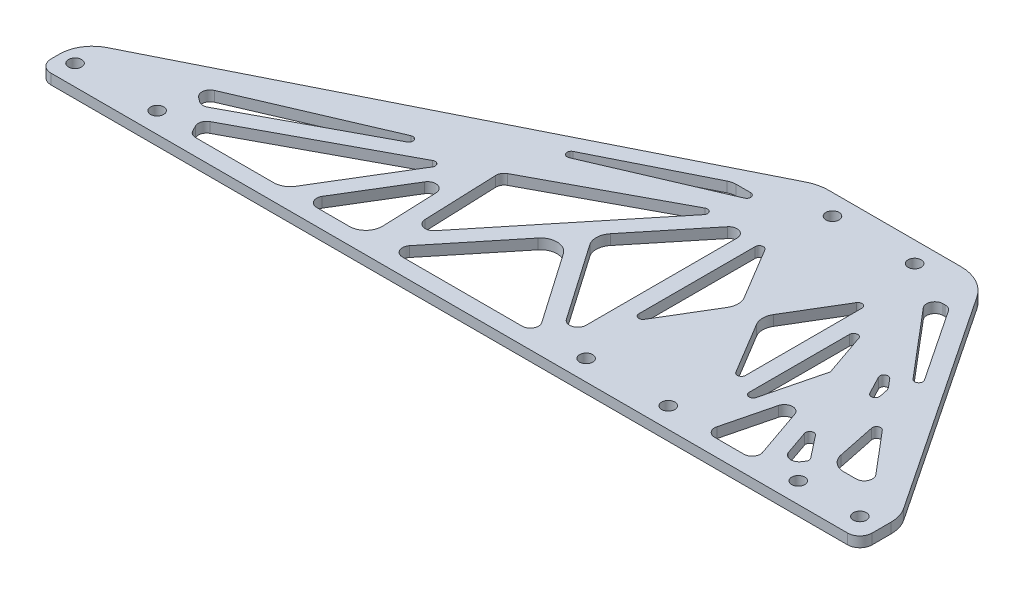
SolidWorks part; units mm, degrees
ref_plane "Front Plane" through (0, 0, 0) normal (0, 0, 1) x (1, 0, 0)
ref_plane "Top Plane" through (0, 0, 0) normal (0, 1, 0) x (1, 0, 0)
ref_plane "Right Plane" through (0, 0, 0) normal (1, 0, 0) x (0, 0, -1)
sketch "Sketch1" plane through (0, 0, 0) normal (0, 1, 0) x (1, 0, 0)
  line L0 (0, 0) -> (254, 0)
  line L2 (203.2, 88.9) -> (152.4, 88.9)
  line L4 (0, 0) -> (0, 12.7)
  line L5 (0, 12.7) -> (152.4, 88.9)
  line L6 (203.2, 88.9) -> (254, 12.7)
  line L7 (254, 12.7) -> (254, 0)
  line L8 (0, 6.35) -> (41.2306, 6.35) construction
  line L9 (254, 6.35) -> (220.1675, 6.35) construction
  line L10 (139.7, 82.55) -> (207.4333, 82.55) construction
  line L11 (156.6333, 76.2) -> (38.0113, 12.7) construction
  line L12 (38.0113, 12.7) -> (22.7185, 24.0592)
  line L13 (226.5259, 15.8112) -> (251.9259, 15.8112)
  line L20 (127, 76.2) -> (211.6667, 76.2)
  line L21 (226.5259, 15.8112) -> (215.9, 0)
  line L22 (38.0113, 12.7) -> (44.45, 0)
  line L23 (156.6333, 76.2) -> (27.2885, 20.6647) construction
  line L24 (156.6333, 76.2) -> (98.8302, 5.08) construction
  line L28 (194.7333, 76.2) -> (226.5259, 15.8112) construction
  line L31 (5.08, 9.5604) -> (153.5992, 83.82)
  line L32 (200.4813, 83.82) -> (153.5992, 83.82)
  line L33 (200.4813, 83.82) -> (248.92, 11.1619)
  line L34 (248.92, 11.1619) -> (248.92, 5.08)
  line L35 (5.08, 5.08) -> (248.92, 5.08)
  line L36 (5.08, 5.08) -> (5.08, 9.5604)
  line L37 (219.314, 5.08) -> (194.7333, 76.2) construction
  line L39 (194.7333, 76.2) -> (245.8205, 15.8112) construction
  line L40 (98.8302, 5.08) -> (97.3223, 44.45) construction
  line L41 (127.7318, 40.64) -> (152.3892, 5.08) construction
  line L42 (207.0237, 40.64) -> (198.1092, 5.08) construction
  line L83 (226.5259, 15.8112) -> (220.2769, 46.0056) construction
  line L84 (207.0237, 40.64) -> (226.5259, 15.8112) construction
  line L107 (97.3223, 44.45) -> (73.4302, 5.08) construction
  line L108 (156.6333, 76.2) -> (194.7333, 12.7) construction
  line L113 (194.7333, 76.2) -> (156.6333, 12.7) construction
  line L114 (155.6312, 78.534) -> (26.2864, 22.9986)
  line L115 (155.4346, 78.4393) -> (36.8125, 14.9393)
  line L116 (154.6622, 77.802) -> (101.1104, 11.9127)
  line L117 (156.6333, 12.7) -> (154.0933, 8.1397)
  line L118 (156.6333, 12.7) -> (194.7333, 12.7)
  line L119 (194.7333, 12.7) -> (200.3598, 0)
  line L120 (153.0965, 6.35) -> (197.5465, 6.35) construction
  line L123 (101.1104, 11.9127) -> (99.5369, 52.9951)
  line L124 (99.5369, 52.9951) -> (96.1931, 47.4852)
  line L125 (125.6445, 39.1927) -> (150.3019, 3.6327)
  line L126 (192.5553, 77.5068) -> (154.4553, 14.0068)
  line L127 (154.4553, 74.8932) -> (192.5553, 11.3932)
  line L128 (156.6333, 12.7) -> (156.6333, 76.2) construction
  line L129 (194.7333, 12.7) -> (194.7333, 76.2) construction
  line L130 (197.2733, 12.7) -> (197.2733, 76.2)
  line L131 (159.1733, 12.7) -> (159.1733, 76.2)
  line L132 (192.1933, 12.7) -> (192.1933, 76.2)
  line L133 (154.0933, 12.7) -> (154.0933, 76.2)
  line L134 (205.8201, 46.2844) -> (228.5234, 17.3801)
  line L137 (205.8201, 46.2844) -> (195.6454, 5.6976)
  line L138 (221.7147, 5.9097) -> (197.134, 77.0297)
  line L139 (192.4858, 75.0167) -> (224.2783, 14.6279)
  line L140 (229.0132, 16.3259) -> (222.7642, 46.5203)
  line L141 (157.6354, 73.866) -> (28.2906, 18.3307)
  line L142 (157.8321, 73.9607) -> (39.21, 10.4607)
  line L143 (158.6044, 74.598) -> (96.5501, -1.7527)
  line L144 (96.5501, -1.7527) -> (95.1077, 35.9049)
  line L145 (95.1077, 35.9049) -> (75.6017, 3.7622)
  line L146 (129.8191, 42.0873) -> (154.4765, 6.5273)
  line L147 (196.9114, 74.8932) -> (158.8114, 11.3932)
  line L148 (158.8114, 77.5068) -> (196.9114, 14.0068)
  line L149 (208.2273, 34.9956) -> (224.5284, 14.2422)
  line L150 (208.2273, 34.9956) -> (200.5729, 4.4624)
  line L151 (216.9134, 4.2503) -> (192.3327, 75.3703)
  line L152 (196.9809, 77.3833) -> (228.7734, 16.9944)
  line L153 (224.0386, 15.2964) -> (217.7896, 45.4908)
  line L154 (71.2588, 6.3978) -> (70.4591, 5.08)
  line L155 (36.8125, 14.9393) -> (35.7571, 14.3744)
  line L156 (39.21, 10.4607) -> (39.1601, 10.434)
  line L157 (154.0933, 12.7) -> (154.0933, 7.0799)
  line L158 (197.2733, 12.7) -> (197.2733, 6.9667)
  line L159 (224.5284, 14.2422) -> (225.0366, 13.5952)
  line L160 (229.0132, 16.3259) -> (229.1197, 15.8112)
  line L161 (192.7942, 74.5595) -> (243.8813, 14.1707)
  line L162 (196.6725, 77.8405) -> (247.7597, 17.4517)
  line L163 (153.766, 7.552) -> (149.5598, 0)
  line L164 (95.5112, 46.3615) -> (71.2588, 6.3978)
  line L165 (99.5369, 52.9951) -> (71.2588, 6.3978) construction
  circle A0 centre (4.8683, 6.35) radius 2.032
  circle A1 centre (30.2683, 6.35) radius 2.032
  circle A2 centre (228.6, 6.35) radius 2.032
  circle A3 centre (247.65, 6.35) radius 2.032
  circle A4 centre (162.9833, 82.55) radius 2.032
  circle A5 centre (188.3833, 82.55) radius 2.032
  circle A28 centre (162.9833, 6.35) radius 2.032
  circle A29 centre (188.3833, 6.35) radius 2.032
  arc A32 (197.2733, 12.7) -> (192.1933, 12.7) centre (194.7333, 12.7) cw
  arc A33 (197.2733, 76.2) -> (192.1933, 76.2) centre (194.7333, 76.2) ccw
  arc A34 (159.1733, 12.7) -> (154.0933, 12.7) centre (156.6333, 12.7) cw
  arc A35 (159.1733, 76.2) -> (154.0933, 76.2) centre (156.6333, 76.2) ccw
  arc A37 (155.6312, 78.534) -> (157.6354, 73.866) centre (156.6333, 76.2) cw
  arc A38 (26.2864, 22.9986) -> (28.2906, 18.3307) centre (27.2885, 20.6647) ccw
  arc A39 (155.4346, 78.4393) -> (157.8321, 73.9607) centre (156.6333, 76.2) cw
  arc A40 (36.8125, 14.9393) -> (39.21, 10.4607) centre (38.0113, 12.7) ccw
  arc A41 (154.6622, 77.802) -> (158.6044, 74.598) centre (156.6333, 76.2) cw
  arc A42 (71.2588, 6.3978) -> (75.6017, 3.7622) centre (73.4302, 5.08) ccw
  arc A43 (125.6445, 39.1927) -> (129.8191, 42.0873) centre (127.7318, 40.64) cw
  arc A44 (150.3019, 3.6327) -> (154.4765, 6.5273) centre (152.3892, 5.08) ccw
  arc A45 (192.5553, 77.5068) -> (196.9114, 74.8932) centre (194.7333, 76.2) cw
  arc A46 (154.4553, 14.0068) -> (158.8114, 11.3932) centre (156.6333, 12.7) ccw
  arc A47 (154.4553, 74.8932) -> (158.8114, 77.5068) centre (156.6333, 76.2) cw
  arc A48 (192.5553, 11.3932) -> (196.9114, 14.0068) centre (194.7333, 12.7) ccw
  arc A49 (228.5234, 17.3801) -> (224.5284, 14.2422) centre (226.5259, 15.8112) cw
  arc A50 (195.6454, 5.6976) -> (200.5729, 4.4624) centre (198.1092, 5.08) ccw
  arc A51 (221.7147, 5.9097) -> (216.9134, 4.2503) centre (219.314, 5.08) cw
  arc A52 (197.134, 77.0297) -> (192.3327, 75.3703) centre (194.7333, 76.2) ccw
  arc A53 (192.4858, 75.0167) -> (196.9809, 77.3833) centre (194.7333, 76.2) cw
  arc A54 (224.2783, 14.6279) -> (228.7734, 16.9944) centre (226.5259, 15.8112) ccw
  arc A55 (229.0132, 16.3259) -> (224.0386, 15.2964) centre (226.5259, 15.8112) cw
  arc A56 (222.7642, 46.5203) -> (217.7896, 45.4908) centre (220.2769, 46.0056) ccw
  arc A57 (192.7942, 74.5595) -> (196.6725, 77.8405) centre (194.7333, 76.2) cw
  arc A58 (243.8813, 14.1707) -> (247.7597, 17.4517) centre (245.8205, 15.8112) ccw
  dimension "D7" = 4.064
  dimension "D8" = 25.4
  dimension "D9" = 132.715
  dimension "D10" = 19.05
  dimension "D11" = 6.35
  dimension "D13" = 19.05
  dimension "D1" = 254
  dimension "D2" = 50.8
  dimension "D3" = 88.9
  dimension "D4" = 152.4
  dimension "D5" = 12.7
  dimension "D6" = 6.35
  dimension "D12" = 25.4
  dimension "D14" = 44.45
  dimension "D15" = 19.05
  dimension "D16" = 25.4
  dimension "D18" = 12.7
  dimension "D19" = 38.1
  dimension "D20" = 19.05
  dimension "D21" = 12.7
  dimension "D22" = 25.4
  dimension "D23" = 50.8
  dimension "D24" = 25.4
  dimension "D29" = 6.35
  dimension "D30" = 38.1
  dimension "D31" = 25.4
  dimension "D32" = 6.35
  dimension "D33" = 2.54
  dimension "D34" = 50.8
  dimension "D35" = 7.552
  dimension "D17" = 5.08
  dimension "D25" = 2.54
  dimension "D26" = 2.54
  dimension "D27" = 2.54
  dimension "D28" = 2.54
  dimension "D37" = 2.54
extrude "Boss-Extrude1" add sketch "Sketch1" along normal blind 3.175 contours L0 L7 L6 L2 L5 L4 | A0 | A1 | A5 | A4 | A2 | A3
extrude "Cut-Extrude2" cut sketch "Sketch1<3>" along normal through all contours L142 L156 L22 L35 L154 L124 | L155 L115 L124 L141 L12 | L144 L145 L35 | L116 L142 L123 | L125 L143 L35 | L157 L133 L143 L146 L117 | L114 L20 L31 | L130 L158 L137 L151 | L35 L151 L150 | L161 L152 L153 | L161 L140 L160 L13 | L159 L149 L138 L21 | L20 L162 L33 | L131 L126 L127 | L147 L148 L132 | L115 L141 L123 | A28 | A29 region at (64.7257, 0, -16.4796) region at (89.2658, 0, -15.355) region at (126.3241, 0, -15.5249) region at (118.3245, 0, -64.21) region at (56.1323, 0, -27.8913) region at (146.3644, 0, -38.8822) region at (115.9087, 0, -40.9571) region at (100.9162, 0, -49.3843) region at (212.3574, 0, -62.2554) region at (208.2553, 0, -13.9673) region at (220.1621, 0, -16.1676) region at (199.6409, 0, -37.9304) region at (163.6893, 0, -44.45) region at (232.1338, 0, -22.7875) region at (215.3763, 0, -44.8583) region at (187.6774, 0, -44.45)
sketch "Sketch1<3>" plane through (0, 0, 0) normal (0, 1, 0) x (1, 0, 0) same geometry as "Sketch1"
fillet "Fillet1" radius 3.81 2 edges at (254, 1.5875, 0) (0, 1.5875, 0)
fillet "Fillet2" radius 10.16 2 edges at (254, 1.5875, -12.7) (0, 1.5875, -12.7)
fillet "Fillet3" radius 12.7 2 edges at (203.2, 1.5875, -88.9) (152.4, 1.5875, -88.9)
fillet "Fillet4" radius 1.27 17 edges at (214.3608, 1.5875, -27.1869) (233.4505, 1.5875, -34.3662) (207.8157, 1.5875, -56.8029) (220.3926, 1.5875, -32.9136) (197.2733, 1.5875, -61.0753) (197.2733, 1.5875, -12.1914) (159.1733, 1.5875, -67.0298) (192.1933, 1.5875, -67.0298) (192.1933, 1.5875, -21.8702) (159.1733, 1.5875, -21.8702) (146.6944, 1.5875, -67.9985) (66.4191, 1.5875, -40.2299) (150.1953, 1.5875, -76.2) (224.7883, 1.5875, -36.74) (103.3533, 1.5875, -50.5595) (90.3319, 1.5875, -37.8269) (225.0366, 1.5875, -13.5952)
fillet "Fillet5" radius 2.54 20 edges at (39.1601, 1.5875, -10.434) (41.8745, 1.5875, -5.08) (99.9212, 1.5875, -42.9602) (101.1104, 1.5875, -11.9127) (95.1077, 1.5875, -35.9049) (76.4014, 1.5875, -5.08) (35.7571, 1.5875, -14.3744) (29.6468, 1.5875, -18.913) (198.0603, 1.5875, -76.2) (205.5613, 1.5875, -76.2) (217.9205, 1.5875, -44.8583) (242.4935, 1.5875, -15.8112) (221.0887, 1.5875, -7.7208) (216.6266, 1.5875, -5.08) (200.7278, 1.5875, -5.08) (207.4116, 1.5875, -31.7419) (154.0933, 1.5875, -69.0476) (149.2983, 1.5875, -5.08) (102.1034, 1.5875, -5.08) (154.0933, 1.5875, -7.0799)
fillet "Fillet6" radius 5.08 8 edges at (229.1197, 1.5875, -15.8112) (96.2884, 1.5875, -5.08) (172.7212, 1.5875, -44.45) (178.6455, 1.5875, -44.45) (130.9066, 1.5875, -40.519) (127.5708, 1.5875, -36.4147) (138.3592, 1.5875, -76.2) (70.4591, 1.5875, -5.08)
